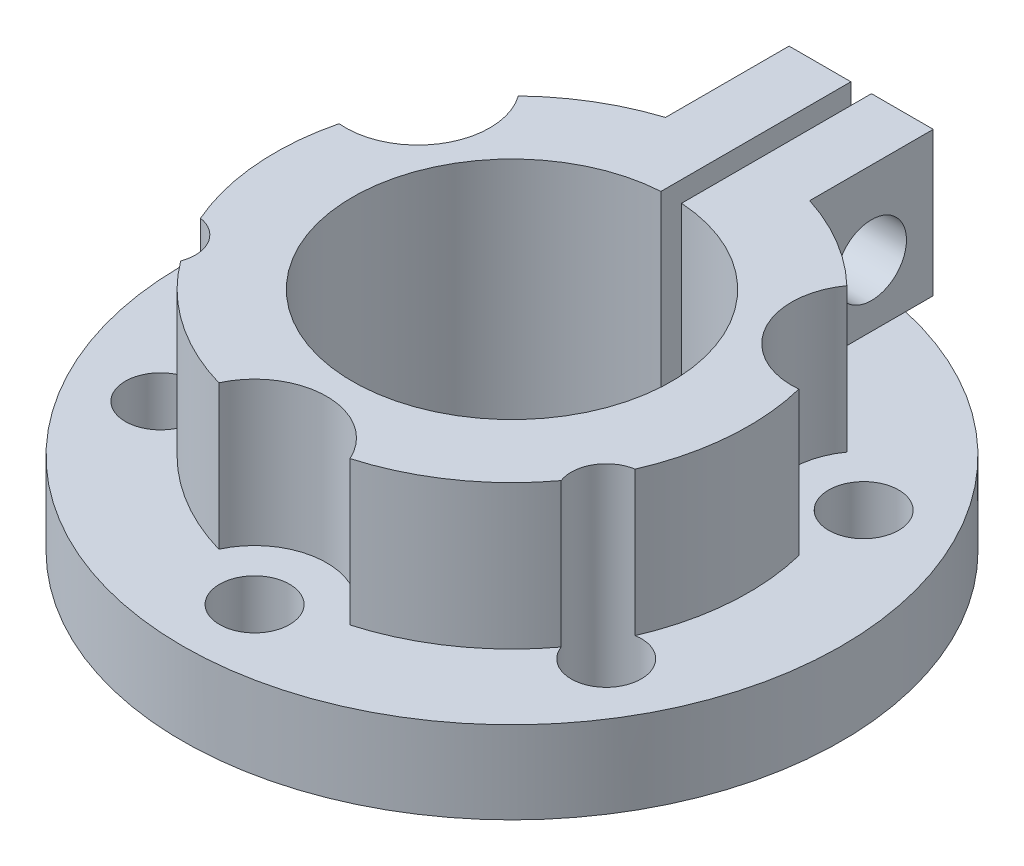
SolidWorks part; units mm, degrees
ref_plane "前视基准面" through (0, 0, 0) normal (0, 0, 1) x (1, 0, 0)
ref_plane "上视基准面" through (0, 0, 0) normal (0, 1, 0) x (1, 0, 0)
ref_plane "右视基准面" through (0, 0, 0) normal (1, 0, 0) x (0, 0, -1)
sketch "草图1" plane through (0, 0, 0) normal (0, 1, 0) x (1, 0, 0)
  circle A0 centre (0, 0) radius 7.75
  circle A1 centre (0, 0) radius 16
  circle A2 centre (0, 0) radius 12.5 construction
  circle A3 centre (0, 12.5) radius 1.7
  circle A4 centre (10.8253, 6.25) radius 1.7
  circle A5 centre (10.8253, -6.25) radius 1.7
  circle A6 centre (0, -12.5) radius 1.7
  circle A7 centre (-10.8253, -6.25) radius 1.7
  circle A8 centre (-10.8253, 6.25) radius 1.7
  dimension "D1" = 25
  dimension "D2" = 15.5
  dimension "D3" = 32
  dimension "D4" = 3.4
  dimension "D5" = 6
extrude "凸台-拉伸1" add sketch "草图1" along normal blind 4
sketch "草图2" plane through (0, 4, 0) normal (0, 1, 0) x (1, 0, 0)
  circle A1 centre (0, -12.5) radius 3.5
  circle A2 centre (-10.8253, 6.25) radius 3.5
  circle A3 centre (10.8253, 6.25) radius 3.5
  circle A4 centre (0, 0) radius 16 construction
  circle A5 centre (0, 0) radius 11.5
  circle A6 centre (0, 0) radius 7.75
  circle A7 centre (0, 0) radius 7.75 construction
  circle M5 centre (-10.8253, -6.25) radius 1.7
  circle M6 centre (10.8253, -6.25) radius 1.7
  circle M7 centre (0, 12.5) radius 1.7
  circle M9 centre (0, 0) radius 7.75
  dimension "D1" = 23
extrude "凸台-拉伸2" add sketch "草图2" along normal blind 7 contours A1 A5 A3 A2 M6 M7 M5 M9 region at (0, 4, 8.6784)
sketch "草图3" plane through (0, 11, 0) normal (0, 1, 0) x (1, 0, 0)
  line L0 (0.5, 0) -> (-0.5, 0)
  line L1 (0.5, -25) -> (-0.5, -25)
  line L2 (0.5, -25) -> (0.5, 25)
  line L3 (0.5, 25) -> (-0.5, 25)
  line L4 (-0.5, -25) -> (-0.5, 25)
  line L5 (0.5, -25) -> (-0.5, 25) construction
  line L6 (0.5, 25) -> (-0.5, -25) construction
  line L8 (-3.5, 10.9545) -> (3.5, 10.9545)
  line L9 (-3.5, 10.9545) -> (-3.5, 16.9545)
  line L10 (-3.5, 16.9545) -> (3.5, 16.9545)
  line L11 (3.5, 10.9545) -> (3.5, 16.9545)
  arc A0 (-1.3165, 11.4244) -> (-7.9768, 8.2837) centre (0, 0) ccw construction
  arc A1 (7.9768, 8.2837) -> (1.3165, 11.4244) centre (0, 0) ccw construction
  arc A2 (-1.3165, 11.4244) -> (1.3165, 11.4244) centre (0, 12.5) ccw construction
  arc A3 (-0.708, 10.9545) -> (0.708, 10.9545) centre (0, 12.5) ccw
  point P0 (0, 0)
  circle M9 centre (0, 0) radius 7.75
  arc M15 (7.9768, 8.2837) -> (1.3165, 11.4244) centre (0, 0) ccw
  arc M16 (1.3165, 11.4244) -> (-1.3165, 11.4244) centre (0, 12.5) cw
  arc M17 (-1.3165, 11.4244) -> (-7.9768, 8.2837) centre (0, 0) ccw
  dimension "D1" = 1
  dimension "D2" = 50
  dimension "D3" = 7
  dimension "D4" = 6
extrude "切除-拉伸1" cut sketch "草图3" against normal blind 11 contours L4 L0 L2 M9 | L4 L10 L2 L3 | L10 L4 L8 L2 | L4 L2 M9 M16 region at (0, 11, -3.8723) region at (0, 11, -9.2848) region at (0, 11, -13.9545) region at (0, 11, -20.9772)
extrude "凸台-拉伸3" add sketch "草图3<3>" against normal up to surface (7 mm away) contours L10 L9 L8 L4 M17 M16 | L11 L10 L2 L8 M15 M16 | L8 L4 M16 | L8 L2 M16 region at (0.5715, 11, -10.9271) region at (-0.5715, 11, -10.9271) region at (2.0028, 11, -14.0716) region at (-2.0028, 11, -14.0716) up to face at (10.8253, 4, -4.55)
sketch "草图3<3>" plane through (0, 11, 0) normal (0, 1, 0) x (1, 0, 0) same geometry as "草图3"
sketch "草图4" plane through (3.5, 0, 0) normal (1, 0, 0) x (0, 0, -1)
  line L0 (16.9545, 4) -> (15.6125, 4) construction
  line L1 (16.9545, 4) -> (16.9545, 11) construction
  circle A0 centre (13.9545, 7) radius 1.7
  circle A1 centre (13.9545, 7) radius 2.5
  dimension "D1" = 3.4
  dimension "D2" = 5
  dimension "D4" = 3
  dimension "D3" = 3
extrude "切除-拉伸2" cut sketch "草图4" against normal blind 8 contours A0
